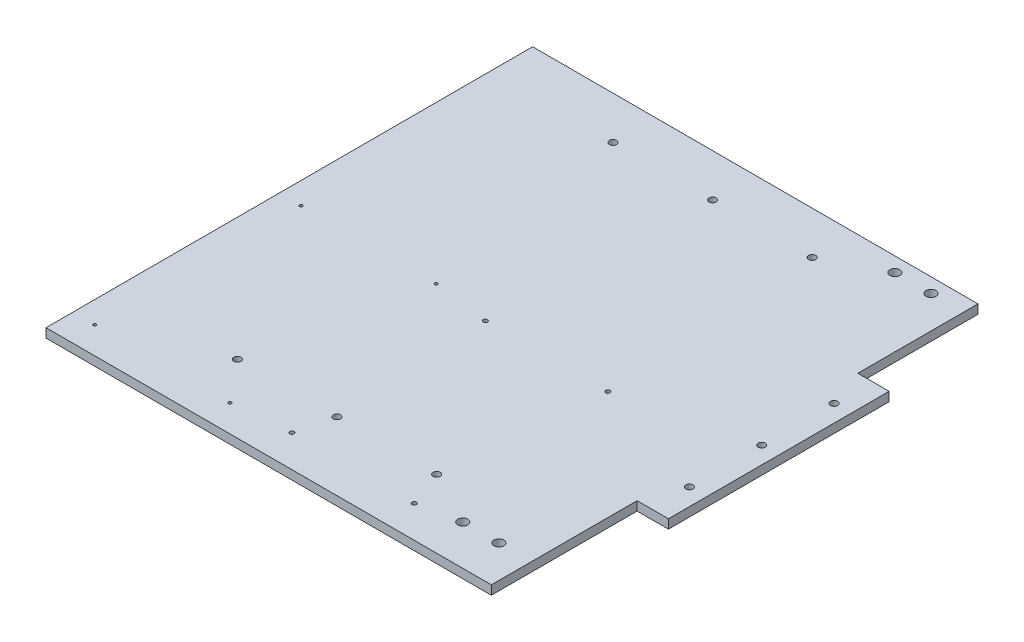
SolidWorks part; units mm, degrees
material "Cedar"
ref_plane "Front Plane" through (0, 0, 0) normal (0, 0, 1) x (1, 0, 0)
ref_plane "Top Plane" through (0, 0, 0) normal (0, 1, 0) x (1, 0, 0)
ref_plane "Right Plane" through (0, 0, 0) normal (1, 0, 0) x (0, 0, -1)
sketch "Sketch1" plane through (0, 0, 0) normal (0, 1, 0) x (1, 0, 0)
  line L0 (72.8376, -16.2766) -> (72.8376, -52.4668) construction
  line L1 (-156.5, -171) -> (156.5, -171)
  line L2 (-156.5, -171) -> (-156.5, 171)
  line L3 (-156.5, 171) -> (156.5, 171)
  line L4 (156.5, -171) -> (156.5, 171)
  line L5 (-156.5, -171) -> (156.5, 171) construction
  line L6 (-156.5, 171) -> (156.5, -171) construction
  point P0 (0, 0)
  dimension "D1" = 342
  dimension "D2" = 313
extrude "Boss-Extrude1" add sketch "Sketch1" against normal blind 6.35
ref_plane "Plane1" through (0, 0, -9) normal (0, 0, -1) x (-1, 0, 0)
sketch "Sketch3" plane through (0, 0, 0) normal (0, 1, 0) x (1, 0, 0)
  line L0 (156.5, 9) -> (-156.5, 9) construction
  line L1 (156.5, -171) -> (156.5, 171) construction
  line L2 (-156.5, 171) -> (-156.5, -171) construction
  line L3 (55, 9) -> (-55, 9) construction
  line L4 (156.5, 86.5702) -> (156.5, -68.5702)
  line L5 (156.5, -68.5702) -> (178.5, -68.5702)
  line L6 (178.5, -68.5702) -> (178.5, 86.5702)
  line L7 (178.5, 86.5702) -> (156.5, 86.5702)
  line L8 (166.5, 59.8) -> (166.5, 9) construction
  circle A0 centre (166.5, 9) radius 2.5
  circle A1 centre (166.5, -41.8) radius 2.5
  circle A2 centre (166.5, 59.8) radius 2.5
  point P10 (156.5, 9)
  dimension "D2" = 5
  dimension "D4" = 5
  dimension "D5" = 50.8
  dimension "D1" = 22
  dimension "D3" = 10
  dimension "D6" = 0
extrude "Boss-Extrude2" add sketch "Sketch3" against normal blind 6.35
sketch "Sketch2" plane through (0, 0, 0) normal (0, 1, 0) x (1, 0, 0)
  line L0 (156.5, 9) -> (-156.5, 9) construction
  line L1 (156.5, -171) -> (156.5, -68.5702) construction
  line L2 (-156.5, 171) -> (-156.5, -171) construction
  line L3 (0, -123) -> (0, -171) construction
  line L4 (55, 9) -> (-55, 9) construction
  line L5 (156.5, -123) -> (-156.5, -123) construction
  line L6 (-156.5, -171) -> (156.5, -171) construction
  circle A0 centre (0, -123) radius 2.5
  circle A1 centre (-70, -123) radius 2.5
  circle A2 centre (70, -123) radius 2.5
  circle A3 centre (-70, 141) radius 2.5
  circle A4 centre (0, 141) radius 2.5
  circle A5 centre (70, 141) radius 2.5
  dimension "D2" = 5
  dimension "D3" = 5
  dimension "D4" = 70
  dimension "D1" = 132
extrude "Cut-Extrude1" cut sketch "Sketch2" against normal through all
sketch "Sketch4" plane through (0, 0, 0) normal (0, 1, 0) x (1, 0, 0)
  line L0 (156.5, -171) -> (156.5, -68.5702) construction
  line L1 (108.24, -142.84) -> (133.64, -142.84) construction
  line L2 (-156.5, -171) -> (156.5, -171) construction
  circle A0 centre (133.64, -142.84) radius 3.5
  circle A1 centre (108.24, -142.84) radius 3.5
  dimension "D1" = 7
  dimension "D2" = 7
  dimension "D3" = 25.4
  dimension "D4" = 22.86
  dimension "D5" = 28.16
extrude "Cut-Extrude2" cut sketch "Sketch4" against normal through all
mirror "Mirror1" about plane through (0, 0, -9) normal (0, 0, -1) of "Cut-Extrude2"
sketch "Sketch5" plane through (0, 0, 0) normal (0, 1, 0) x (1, 0, 0)
  circle A29 centre (79.77, -148.4704) radius 1.5
  circle A30 centre (-6.23, -148.4704) radius 1.5
  circle A31 centre (-6.23, -12.4704) radius 1.5
  circle A32 centre (79.77, -12.4704) radius 1.5
  circle A33 centre (-46.1139, -7.1139) radius 1.05
  circle A34 centre (-46.1139, -152.1139) radius 1.05
  circle A35 centre (-141.1139, -7.1139) radius 1.05
  circle A36 centre (-141.1139, -152.1139) radius 1.05
extrude "Cut-Extrude3" cut sketch "Sketch5" against normal through all
